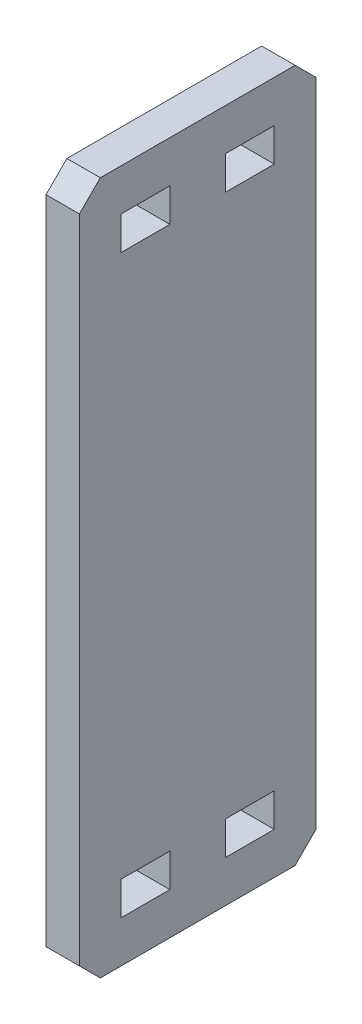
SolidWorks part; units mm, degrees
ref_plane "Front" through (0, 0, 0) normal (0, 0, 1) x (1, 0, 0)
ref_plane "Top" through (0, 0, 0) normal (0, 1, 0) x (1, 0, 0)
ref_plane "Right" through (0, 0, 0) normal (1, 0, 0) x (0, 0, -1)
ref_axis "side-side" through (80.9, 0, 0) along (-1, 0, 0)
ref_axis "up-down" through (0, 50, 0) along (0, -1, 0)
ref_axis "front-back" through (0, 0, -80.9) along (0, 0, 1)
sketch "Sketch1" plane through (0, 0, 0) normal (1, 0, 0) x (0, 0, -1)
  line L1 (-89.4373, 63.246) -> (-132.6173, 63.246)
  line L2 (-89.4373, 63.246) -> (-89.4373, -63.246)
  line L3 (-89.4373, -63.246) -> (-132.6173, -63.246)
  line L4 (-132.6173, 63.246) -> (-132.6173, -63.246)
  line L9 (-97.0573, 55.626) -> (-105.9473, 55.626)
  line L10 (-97.0573, 55.626) -> (-97.0573, 49.53)
  line L11 (-97.0573, 49.53) -> (-105.9473, 49.53)
  line L12 (-124.9973, 55.626) -> (-124.9973, 49.53)
  line L13 (-97.0573, -49.53) -> (-105.9473, -49.53)
  line L14 (-97.0573, -49.53) -> (-97.0573, -55.626)
  line L15 (-97.0573, -55.626) -> (-105.9473, -55.626)
  line L16 (-124.9973, -49.53) -> (-124.9973, -55.626)
  line L18 (-105.9473, 55.626) -> (-105.9473, 49.53) construction
  line L19 (-105.9473, 55.626) -> (-105.9473, 49.53)
  line L20 (-116.1073, 55.626) -> (-116.1073, 49.53) construction
  line L21 (-116.1073, 55.626) -> (-116.1073, 49.53)
  line L22 (-116.1073, 55.626) -> (-124.9973, 55.626)
  line L23 (-116.1073, 49.53) -> (-124.9973, 49.53)
  line L24 (-116.1073, -49.53) -> (-116.1073, -55.626) construction
  line L25 (-116.1073, -49.53) -> (-116.1073, -55.626)
  line L26 (-105.9473, -49.53) -> (-105.9473, -55.626) construction
  line L27 (-105.9473, -49.53) -> (-105.9473, -55.626)
  line L28 (-116.1073, -49.53) -> (-124.9973, -49.53)
  line L29 (-116.1073, -55.626) -> (-124.9973, -55.626)
extrude "Boss-Extrude1" add sketch "Sketch1" along normal mid plane 6.096
chamfer "Chamfer1" distance 3.81 angle 45 4 edges at (0, -63.246, 89.4373) (0, -63.246, 132.6173) (0, 63.246, 89.4373) (0, 63.246, 132.6173)
